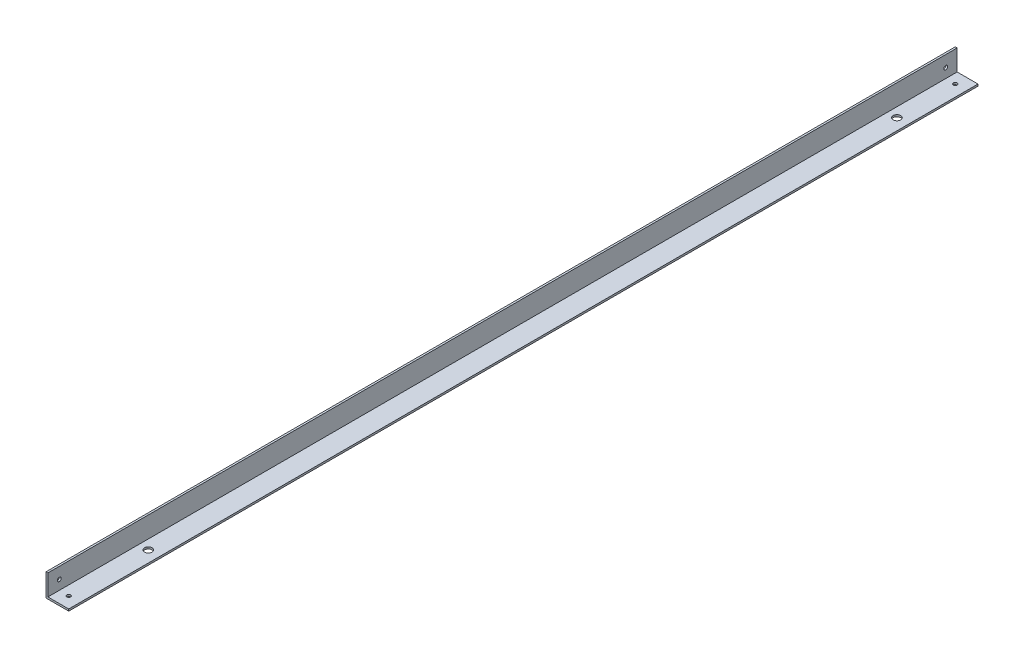
SolidWorks part; units mm, degrees
material "1060 Alloy"
ref_plane "Front Plane" through (0, 0, 0) normal (0, 0, 1) x (1, 0, 0)
ref_plane "Top Plane" through (0, 0, 0) normal (0, 1, 0) x (1, 0, 0)
ref_plane "Right Plane" through (0, 0, 0) normal (1, 0, 0) x (0, 0, -1)
sketch "Sketch1" plane through (0, 0, 0) normal (0, 0, 1) x (1, 0, 0)
  line L0 (0, 0) -> (0, 19.05)
  line L1 (0, 0) -> (19.05, 0)
  line L2 (0, 19.05) -> (1.5875, 19.05)
  line L3 (19.05, 0) -> (19.05, 1.5875)
  line L4 (19.05, 1.5875) -> (1.5875, 1.5875)
  line L5 (1.5875, 1.5875) -> (1.5875, 19.05)
  dimension "D1" = 19.05
  dimension "D2" = 19.05
  dimension "D3" = 1.5875
  dimension "D4" = 1.5875
extrude "Boss-Extrude1" add sketch "Sketch1" against normal blind 762
ref_axis "Axis1" through (0, 0, 0) along (0.7071, 0.7071, 0)
ref_plane "Plane1" through (0, 0, 0) normal (-0.7071, 0.7071, 0) x (0.7071, 0.7071, 0)
sketch "Sketch2" plane through (0, 1.5875, 0) normal (0, 1, 0) x (1, 0, 0)
  line L0 (1.5875, 762) -> (9.525, 762)
  line L1 (19.05, 0) -> (1.5875, 0) construction
  line L2 (9.525, 9.525) -> (9.525, 50009.525) construction
  line L3 (19.05, 762) -> (1.5875, 762) construction
  line L4 (9.525, 9.525) -> (1.5875, 9.525) construction
  line L5 (1.5875, 762) -> (1.5875, 0) construction
  line L6 (9.525, 762) -> (9.525, 752.475) construction
  circle A0 centre (9.525, 9.525) radius 1.5875
  circle A5 centre (9.525, 752.475) radius 1.5875
  circle A6 centre (9.525, 76.2) radius 3.175
  circle A7 centre (9.525, 703.58) radius 3.175
  dimension "D2" = 6.35
  dimension "D3" = 9.525
  dimension "D4" = 3.175
  dimension "D6" = 6.35
  dimension "D8" = 3.175
  dimension "D5" = 76.2
  dimension "D7" = 58.42
  dimension "D9" = 7.9375
  dimension "D10" = 9.525
extrude "Cut-Extrude2" cut sketch "Sketch2" against normal blind 2.794 contours A0 | A5 | A6 | A7
sketch "Sketch4" plane through (1.5875, 0, 0) normal (1, 0, 0) x (0, 0, -1)
  line L0 (752.475, 9.525) -> (762, 9.525) construction
  line L1 (0, 19.05) -> (0, 0) construction
  line L2 (0, 9.525) -> (50000, 9.525) construction
  line L3 (0, 1.5875) -> (0, 19.05) construction
  line L4 (0, 1.5875) -> (0, 9.525)
  line L5 (762, 1.5875) -> (762, 19.05) construction
  circle A0 centre (9.525, 9.525) radius 1.5875
  circle A2 centre (752.475, 9.525) radius 1.5875
  dimension "D1" = 9.525
  dimension "D2" = 3.175
  dimension "D3" = 9.525
  dimension "D4" = 3.175
  dimension "D12" = 7.9375
extrude "Cut-Extrude3" cut sketch "Sketch4" against normal blind 8.89 contours A2 | A0
mirror "Mirror1" about plane through (19.05, 0, -762) normal (1, 0, 0) of "Cut-Extrude3", "Boss-Extrude1", "Cut-Extrude2"
sketch "Sketch5" plane through (0, 0, 0) normal (0, 0, 1) x (1, 0, 0)
  line L0 (0, 0) -> (38.1, 0) construction
  line L1 (0, 19.05) -> (19.05, 19.05)
  line L2 (0, 19.05) -> (0, 0)
  line L3 (0, 0) -> (19.05, 0)
  line L4 (19.05, 19.05) -> (19.05, 0)
extrude "Cut-Extrude4" cut sketch "Sketch5" against normal through all flip side to cut
